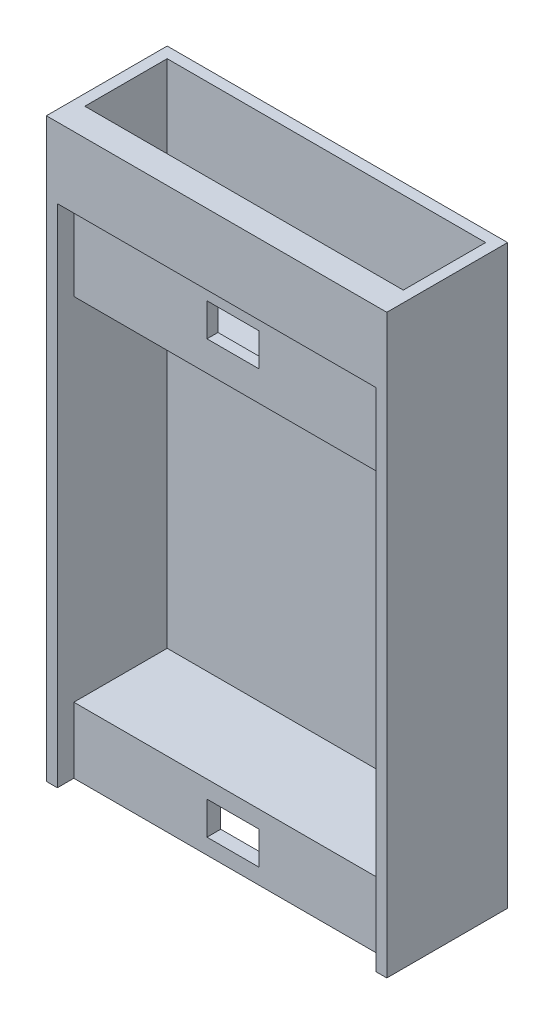
SolidWorks part; units mm, degrees
ref_plane "Front Plane" through (0, 0, 0) normal (0, 0, 1) x (1, 0, 0)
ref_plane "Top Plane" through (0, 0, 0) normal (0, 1, 0) x (1, 0, 0)
ref_plane "Right Plane" through (0, 0, 0) normal (1, 0, 0) x (0, 0, -1)
sketch "Sketch1" plane through (0, 0, 0) normal (0, 0, 1) x (1, 0, 0)
  line L1 (-31, 39) -> (31, 39)
  line L2 (-31, 39) -> (-31, -39)
  line L3 (-31, -39) -> (31, -39)
  line L4 (31, 39) -> (31, -39)
  point P4 (0, 39)
  point P6 (-31, 0)
  dimension "D1" = 62
  dimension "D2" = 78
extrude "Boss-Extrude1" add sketch "Sketch1" against normal blind 2
sketch "Sketch2" plane through (0, 0, 0) normal (0, 0, 1) x (1, 0, 0)
  line L1 (-31, 39) -> (31, 39)
  line L2 (-31, 39) -> (-31, -39)
  line L3 (-31, -39) -> (31, -39)
  line L4 (31, 39) -> (31, -39)
  line L5 (29, -27) -> (-29, -27)
  line L6 (29, -27) -> (29, 37)
  line L7 (29, 37) -> (-29, 37)
  line L8 (-29, -27) -> (-29, 37)
  dimension "D1" = 2
  dimension "D2" = 2
  dimension "D3" = 12
  dimension "D4" = 2
extrude "Boss-Extrude2" add sketch "Sketch2" along normal blind 20
sketch "Sketch3" plane through (0, 37, 0) normal (0, -1, 0) x (1, 0, 0)
  circle A0 centre (-20.4882, 8.7676) radius 3.3131
extrude "Cut-Extrude1" cut sketch "Sketch3" against normal up to next
sketch "Sketch4" plane through (0, 0, 0) normal (0, 0, 1) x (1, 0, 0)
  line L0 (31, -39) -> (31, 39) construction
  line L2 (-31, 39) -> (-31, 66)
  line L3 (-31, 66) -> (31, 66)
  line L4 (31, 39) -> (31, 66)
  line L10 (-31, 39) -> (31, 39)
  dimension "D1" = 27
extrude "Boss-Extrude3" add sketch "Sketch4" against normal blind 2
sketch "Sketch5" plane through (0, 0, 0) normal (0, 0, 1) x (1, 0, 0)
  line L0 (-31, 39) -> (-31, 66)
  line L2 (31, 66) -> (31, 39)
  line L3 (31, 39) -> (29, 39)
  line L4 (-31, 39) -> (31, 39) construction
  line L5 (29, 39) -> (29, 66)
  line L7 (-29, 66) -> (-29, 39)
  line L8 (-29, 39) -> (-31, 39)
  line L9 (31, 66) -> (-31, 66) construction
  line L11 (31, 66) -> (29, 66)
  line L12 (-29, 66) -> (-31, 66)
  dimension "D1" = 2
  dimension "D2" = 2
extrude "Boss-Extrude4" add sketch "Sketch5" along normal blind 20
sketch "Sketch6" plane through (0, 0, 20) normal (0, 0, 1) x (1, 0, 0)
  line L1 (-29, 66) -> (29, 66)
  line L2 (-29, 66) -> (-29, 39)
  line L3 (-29, 39) -> (29, 39)
  line L4 (29, 66) -> (29, 39)
  line L5 (-29, 39) -> (-29, 66) construction
  line L6 (29, 66) -> (-29, 66) construction
extrude "Boss-Extrude5" add sketch "Sketch6" against normal blind 2
sketch "Sketch9" plane through (0, 0, 0) normal (0, 0, 1) x (1, 0, 0)
  line L0 (-31, -39) -> (31, -39) construction
  line L1 (28.8739, -29) -> (-29, -29)
  line L2 (28.8739, -29) -> (28.8739, -39)
  line L3 (28.8739, -39) -> (-29, -39)
  line L4 (-29, -29) -> (-29, -39)
  line L5 (-29, 37) -> (-29, -27) construction
  line L6 (-29, -27) -> (29, -27) construction
  dimension "D1" = 2
extrude "Cut-Extrude4" cut sketch "Sketch9" along normal blind 14.5
sketch "Sketch12" plane through (0, 0, 18) normal (0, 0, -1) x (-1, 0, 0)
  line L1 (-29, 66) -> (29, 66)
  line L2 (-29, 66) -> (-29, 39)
  line L3 (-29, 39) -> (29, 39)
  line L4 (29, 66) -> (29, 39)
extrude "Boss-Extrude6" add sketch "Sketch12" along normal blind 3
sketch "Sketch13" plane through (0, 0, 20) normal (0, 0, 1) x (1, 0, 0)
  line L0 (-31, -39) -> (31, -39) construction
  line L1 (-29, 53.1439) -> (29, 53.1439)
  line L2 (-29, 53.1439) -> (-29, -39)
  line L3 (-29, -39) -> (29, -39)
  line L4 (29, 53.1439) -> (29, -39)
  line L5 (31, -39) -> (31, 66) construction
  line L6 (-31, 66) -> (-31, -39) construction
  dimension "D1" = 2
  dimension "D2" = 2
  dimension "D3" = 92.1439
extrude "Cut-Extrude6" cut sketch "Sketch13" against normal blind 3
sketch "Sketch14" plane through (0, 0, 17) normal (0, 0, 1) x (1, 0, 0)
  line L1 (-4.75, 48.4392) -> (4.75, 48.4392)
  line L2 (-4.75, 48.4392) -> (-4.75, 42.4392)
  line L3 (-4.75, 42.4392) -> (4.75, 42.4392)
  line L4 (4.75, 48.4392) -> (4.75, 42.4392)
  line L5 (-4.75, -30.1608) -> (4.75, -30.1608)
  line L6 (-4.75, -30.1608) -> (-4.75, -36.1608)
  line L7 (-4.75, -36.1608) -> (4.75, -36.1608)
  line L8 (4.75, -30.1608) -> (4.75, -36.1608)
  line L9 (29, 53.1439) -> (-29, 53.1439) construction
  point P8 (0, 48.4392)
  point P10 (0, -30.1608)
  point P11 (4.75, -33.1608)
  point P14 (4.75, 45.4392)
  dimension "D1" = 9.5
  dimension "D2" = 6
  dimension "D3" = 78.6
extrude "Cut-Extrude7" cut sketch "Sketch14" against normal up to surface (17 mm away) up to face at (-0.0631, -34, 0)
equation "\"batteries_width\"=55"
equation "\"padding\"=1.5"
equation "\"D1@Sketch1\"=\"padding\"*2+\"batteries_width\"+\"wall\"*2"
equation "\"batteries_height\"=61"
equation "\"D2@Sketch1\"=\"batteries_height\"+\"padding\"*2+\"wall\"*2+10"
equation "\"wall\"=2"
equation "\"D1@Boss-Extrude1\"=\"wall\""
equation "\"D1@Sketch2\"=\"wall\""
equation "\"D2@Sketch2\"=\"wall\""
equation "\"D3@Sketch2\"=\"wall\"+10"
equation "\"D4@Sketch2\"=\"wall\""
equation "\"D1@Sketch4\"=25+\"wall\""
equation "\"D1@Boss-Extrude3\"=\"wall\""
equation "\"D1@Sketch5\"=\"wall\""
equation "\"D2@Sketch5\"=\"wall\""
equation "\"D1@Sketch9\"=\"wall\""
equation "\"D1@Sketch13\"=\"wall\""
equation "\"D2@Sketch13\"=\"wall\""
